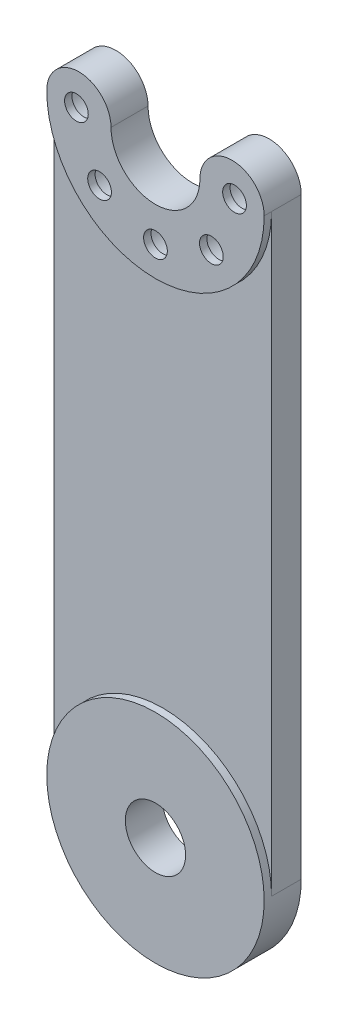
SolidWorks part; units mm, degrees
ref_plane "Plano frontal" through (0, 0, 0) normal (0, 0, 1) x (1, 0, 0)
ref_plane "Plano superior" through (0, 0, 0) normal (0, 1, 0) x (1, 0, 0)
ref_plane "Plano direito" through (0, 0, 0) normal (1, 0, 0) x (0, 0, -1)
other "Centro da massa"
sketch "Esboço1" plane through (0, 0, 0) normal (0, 0, 1) x (1, 0, 0)
  arc A2 (-4.5, 0) -> (4.5, 0) centre (0, 0) ccw
  arc A3 (11, 0) -> (-11, 0) centre (0, 0) cw
  arc A4 (-4, 0) -> (4, 0) centre (0, 0) ccw construction
  arc A5 (11, 0) -> (4.5, 0) centre (7.75, 0) ccw
  arc A6 (-4.5, 0) -> (-11, 0) centre (-7.75, 0) ccw
  arc A9 (-11, 0) -> (11, 0) centre (0, 0) ccw construction
  dimension "D1" = 0.5
extrude "Ressalto-extrusão1" add sketch "Esboço1" against normal offset from surface (0.75 mm away) 2 offset beyond the face yes
sketch "Esboço3" plane through (0, 0, -0.75) normal (0, 0, -1) x (-1, 0, 0)
  line L0 (-11, 0) -> (-11, -60)
  line L2 (11, -60) -> (11, 0)
  arc A0 (11, 0) -> (4.5, 0) centre (7.75, 0) ccw construction
  arc A1 (-4.5, 0) -> (4.5, 0) centre (0, 0) ccw construction
  arc A2 (-4.5, 0) -> (-11, 0) centre (-7.75, 0) ccw construction
  arc A3 (11, 0) -> (4.5, 0) centre (7.75, 0) ccw
  arc A4 (-4.5, 0) -> (4.5, 0) centre (0, 0) ccw
  arc A5 (-4.5, 0) -> (-11, 0) centre (-7.75, 0) ccw
  arc A9 (-11, -60) -> (11, -60) centre (0, -60) ccw
extrude "Ressalto-extrusão2" add sketch "Esboço3" along normal blind 3
hole_wizard "Rebaixo para SHCS M21" positions "Sketch1" profile "Sketch2" counterbore size "M2" standard "Ansi Metric" end condition up to next
sketch "Sketch1" plane through (0, 0, -3.75) normal (0, 0, -1) x (-1, 0, 0)
  line L0 (0, 0) -> (-8, 0) construction
  line L1 (0, 0) -> (-5.6569, -5.6569) construction
  line L2 (0, 0) -> (0, -8) construction
  line L3 (0, 0) -> (5.6569, -5.6569) construction
  line L4 (0, 0) -> (8, 0) construction
  arc A0 (-9, 0) -> (-7, 0) centre (-8, 0) ccw construction
  point P0 (-8, 0)
  point P16 (-5.6569, -5.6569)
  point P18 (0, -8)
  point P20 (5.6569, -5.6569)
  point P22 (8, 0)
  dimension "D1" = 5
sketch "Sketch2" plane through (8, 0, -3.75) normal (1, 0, 0) x (0, 1, 0)
  line L0 (0, 0) -> (0, 3.75)
  line L1 (0, 3.75) -> (1.2, 3.75)
  line L3 (1.2, 3.75) -> (1.2, 3)
  line L4 (1.2, 3) -> (2.2, 3)
  line L5 (2.2, 3) -> (2.2, 0)
  line L7 (2.2, 0) -> (0, 0)
  line L11 (0, -6.35) -> (0, 107.95) construction
  dimension "Thru Hole Dia." = 2.4
  dimension "Thru Hole Depth" = 3.75
  dimension "C'Bore Dia." = 4.4
  dimension "C'Bore Depth" = 3
sketch "Esboço4" plane through (0, 0, -0.75) normal (0, 0, 1) x (1, 0, 0)
  circle A0 centre (0, -60) radius 11
  arc A1 (-11, -60) -> (11, -60) centre (0, -60) ccw construction
extrude "Ressalto-extrusão3" add sketch "Esboço4" along normal up to surface (0.75 mm away)
sketch "Esboço5" plane through (0, 0, -3.75) normal (0, 0, -1) x (-1, 0, 0)
  circle A0 centre (0, -60) radius 3.05 construction
  circle A1 centre (0, -60) radius 3.05
extrude "Corte-extrusão1" cut sketch "Esboço5" against normal through all
